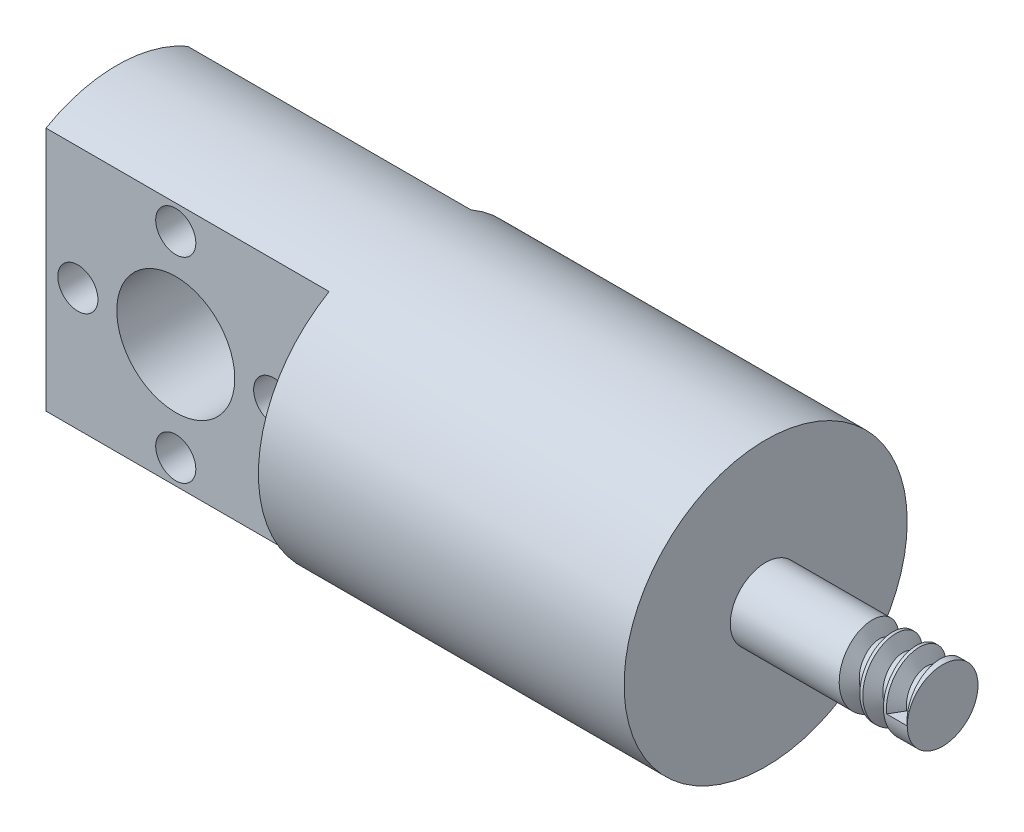
SolidWorks part; units mm, degrees
material "AISI 1020"
ref_plane "Plano frontal" through (0, 0, 0) normal (0, 0, 1) x (1, 0, 0)
ref_plane "Plano superior" through (0, 0, 0) normal (0, 1, 0) x (1, 0, 0)
ref_plane "Plano direito" through (0, 0, 0) normal (1, 0, 0) x (0, 0, -1)
sketch "Esboço1" plane through (0, 0, 0) normal (1, 0, 0) x (0, 0, -1)
  circle A0 centre (0, 0) radius 12
  dimension "D1" = 24
extrude "Ressalto-extrusão1" add sketch "Esboço1" along normal blind 70
sketch "Esboço2" plane through (70, 0, 0) normal (1, 0, 0) x (0, 0, -1)
  circle A0 centre (0, 0) radius 12
  circle A1 centre (0, 0) radius 3
  dimension "D1" = 6
  dimension "D2" = 24
extrude "Corte-extrusão3" cut sketch "Esboço2" against normal blind 15
thread "Rosca2" pitch 2 method cut profile "Perfil da rosca2" start angle 0, offset 0, length 5, pitch 2, diameter 6
ref_plane "Plano2" through (70, 0, 3) normal (0, -1, 0) x (0, 0, 1)
sketch "Perfil da rosca2" plane through (70, 0, 3) normal (0, -1, 0) x (0, 0, 1)
  line L0 (0, 0) -> (0, 2) construction
  line L11 (0, 0) -> (0, 1.75)
  line L12 (0, 1.75) -> (-1.0825, 1.125)
  line L13 (-1.0825, 1.125) -> (-1.0825, 0.625)
  line L15 (-1.0825, 0.625) -> (0, 0)
  line L17 (-1.0825, 0.875) -> (0, 0.875) construction
  point P2 (0, 0)
  dimension "Pitch" = 2
  dimension "Profile_Angle" = 60
  dimension "Profile_Land" = 0.5
  dimension "Profile_Height" = 1.0825
sketch "Esboço7" plane through (0, 0, 0) normal (0, 0, 1) x (1, 0, 0)
  line L0 (11, 14.9088) -> (11, -17.0589) construction
  line L1 (20.9021, 0) -> (-3.7254, 0) construction
  circle A4 centre (11, 0) radius 5
  circle A5 centre (11, 8.3) radius 1.7
  circle A6 centre (11, -8.3) radius 1.7
  circle A7 centre (2.7, 0) radius 1.7
  circle A8 centre (19.3, 0) radius 1.7
  dimension "D3" = 8.3
  dimension "D10" = 10
  dimension "D2" = 3.4
  dimension "D4" = 8.3
  dimension "D5" = 2.7
extrude "Corte-extrusão4" cut sketch "Esboço7" against normal through all and the other way through all
sketch "Esboço8" plane through (0, 0, 0) normal (-1, 0, 0) x (0, 0, 1)
  line L1 (-12.0051, -11.9579) -> (12.0051, -11.9579)
  line L2 (-12.0051, -11.9579) -> (-12.0051, 11.9579)
  line L3 (-12.0051, 11.9579) -> (12.0051, 11.9579)
  line L4 (12.0051, -11.9579) -> (12.0051, 11.9579)
  line L5 (-12.0051, -11.9579) -> (12.0051, 11.9579) construction
  line L6 (-12.0051, 11.9579) -> (12.0051, -11.9579) construction
  line L7 (-6.0051, 11.9579) -> (-12.0051, 11.9579)
  line L8 (-6.0051, 11.9579) -> (-6.0051, -11.9579)
  line L9 (-6.0051, -11.9579) -> (-12.0051, -11.9579)
  line L10 (-12.0051, 11.9579) -> (-12.0051, -11.9579)
  line L11 (12.0051, 11.9579) -> (6.0051, 11.9579)
  line L12 (12.0051, 11.9579) -> (12.0051, -11.9579)
  line L13 (12.0051, -11.9579) -> (6.0051, -11.9579)
  line L14 (6.0051, 11.9579) -> (6.0051, -11.9579)
  point P0 (0, 0)
  circle M5 centre (0, 0) radius 12
  dimension "D1" = 6
  dimension "D2" = 6
extrude "Corte-extrusão5" cut sketch "Esboço8" against normal blind 24 contours L8 M5 | L14 M5 region at (0, 0, -8.4632) region at (0, 0, 8.4632)
